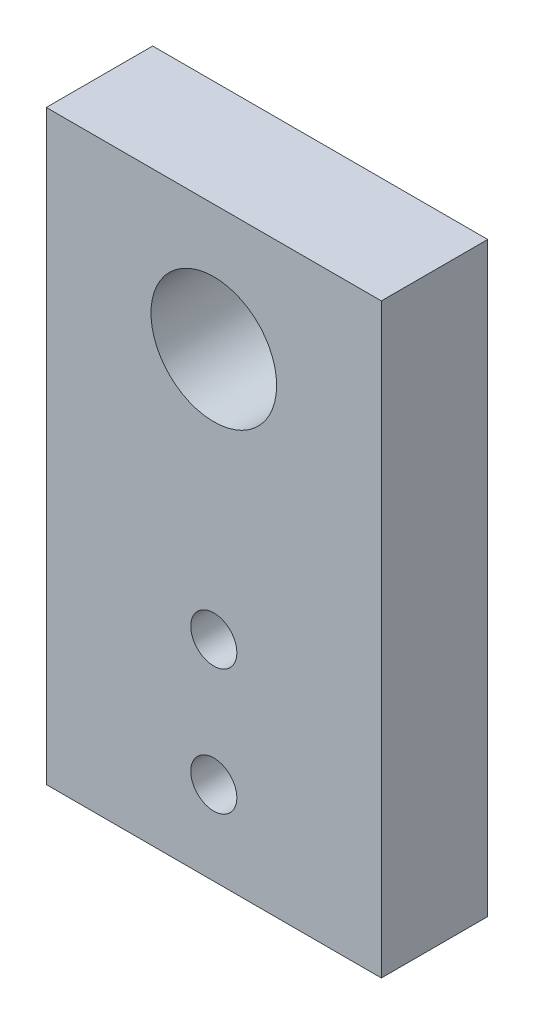
SolidWorks part; units mm, degrees
material "6061 Alloy"
ref_plane "Front Plane" through (0, 0, 0) normal (0, 0, 1) x (1, 0, 0)
ref_plane "Top Plane" through (0, 0, 0) normal (0, 1, 0) x (1, 0, 0)
ref_plane "Right Plane" through (0, 0, 0) normal (1, 0, 0) x (0, 0, -1)
sketch "Sketch1" plane through (0, 0, 0) normal (0, 0, 1) x (1, 0, 0)
  line L0 (0, 35) -> (0, -35) construction
  line L1 (-20, -35) -> (20, -35)
  line L2 (-20, -35) -> (-20, 35)
  line L3 (-20, 35) -> (20, 35)
  line L4 (20, -35) -> (20, 35)
  line L5 (-20, -35) -> (20, 35) construction
  line L6 (-20, 35) -> (20, -35) construction
  circle A0 centre (0, 20) radius 7.5
  circle A1 centre (0, -10) radius 2.5 construction
  circle A2 centre (0, -25) radius 2.5 construction
  point P4 (0, 0)
  dimension "D3" = 15
  dimension "D4" = 5
  dimension "D5" = 5
  dimension "D1" = 40
  dimension "D2" = 70
  dimension "D6" = 10
  dimension "D7" = 15
  dimension "D8" = 55
extrude "Boss-Extrude1" add sketch "Sketch1" along normal blind 12.7
hole_wizard "M5 Clearance Hole1" positions "Sketch4" profile "Sketch5" hole size "M5" standard "ISO" end condition through all
sketch "Sketch4" plane through (0, 0, 12.7) normal (0, 0, 1) x (1, 0, 0)
  point P0 (0, -10)
  point P3 (0, -25)
sketch "Sketch5" plane through (0, -10, 12.7) normal (1, 0, 0) x (0, -1, 0)
  line L0 (0, 0) -> (0, 12.7)
  line L1 (0, 12.7) -> (2.75, 12.7)
  line L2 (2.75, 12.7) -> (2.75, 0)
  line L5 (2.75, 0) -> (0, 0)
  line L11 (0, -6.35) -> (0, 107.95) construction
  dimension "Thru Hole Dia." = 5.5
  dimension "Thru Hole Depth" = 12.7
